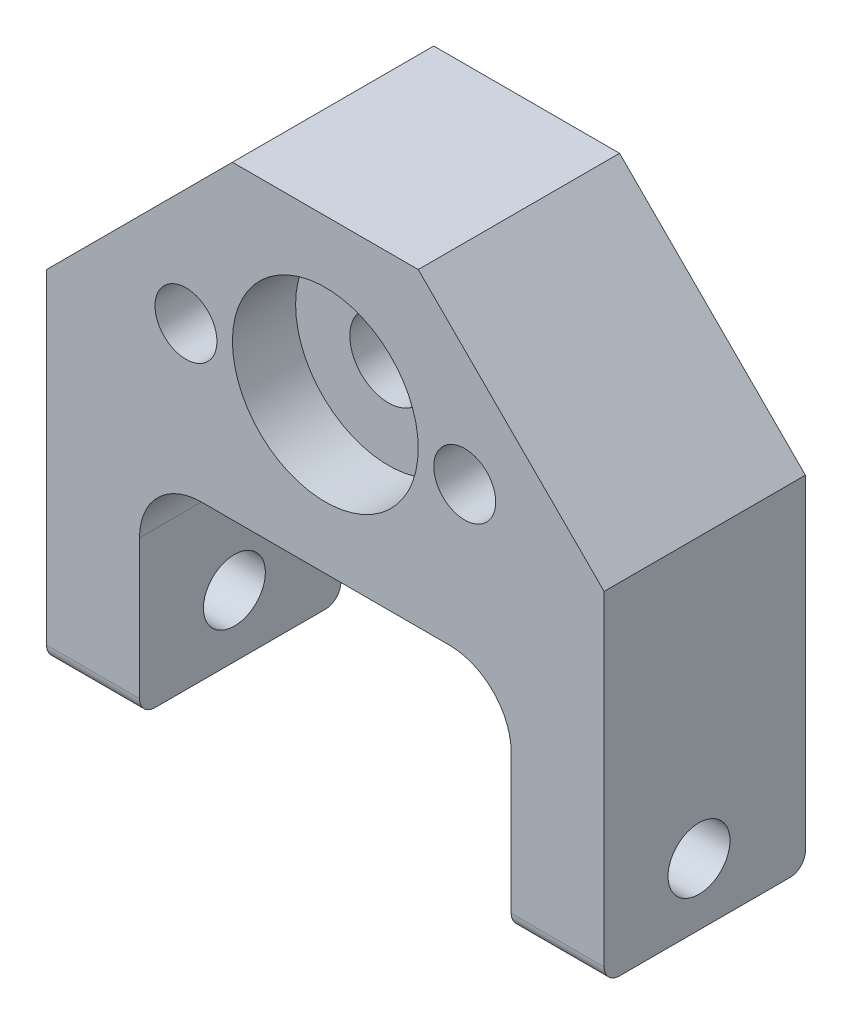
SolidWorks part; units mm, degrees
material "6063-O"
ref_plane "Front" through (0, 0, 0) normal (0, 0, 1) x (1, 0, 0)
ref_plane "Top" through (0, 0, 0) normal (0, 1, 0) x (1, 0, 0)
ref_plane "Right" through (0, 0, 0) normal (1, 0, 0) x (0, 0, -1)
sketch "Sketch1" plane through (0, 0, 0) normal (0, 0, 1) x (1, 0, 0)
  line L1 (28.575, -15.875) -> (-28.575, -15.875)
  line L2 (28.575, -15.875) -> (28.575, 15.875)
  line L3 (28.575, 15.875) -> (-28.575, 15.875)
  line L4 (-28.575, -15.875) -> (-28.575, 15.875)
  line L5 (28.575, -15.875) -> (-28.575, 15.875) construction
  line L6 (28.575, 15.875) -> (-28.575, -15.875) construction
  point P0 (0, 0)
  dimension "D1" = 31.75
  dimension "D2" = 57.15
extrude "Boss-Extrude1" add sketch "Sketch1" along normal blind 20.6375
sketch "Sketch2" plane through (0, 0, 0) normal (0, 0, -1) x (-1, 0, 0)
  circle A0 centre (0, 0) radius 11.1125
  dimension "D1" = 22.225
extrude "Cut-Extrude1" cut sketch "Sketch2" against normal blind 6.985
sketch "Sketch3" plane through (0, 0, 6.985) normal (0, 0, -1) x (-1, 0, 0)
  circle A0 centre (0, 0) radius 8.255
  dimension "D1" = 16.51
extrude "Cut-Extrude2" cut sketch "Sketch3" against normal blind 2.413
sketch "Sketch4" plane through (0, 0, 9.398) normal (0, 0, -1) x (-1, 0, 0)
  circle A0 centre (0, 0) radius 3.9688
  dimension "D1" = 7.9375
extrude "Cut-Extrude3" cut sketch "Sketch4" against normal through all
sketch "Sketch6" plane through (0, 0, 9.398) normal (0, 0, -1) x (-1, 0, 0)
  circle A0 centre (0, 0) radius 9.525
  dimension "D1" = 19.05
extrude "Cut-Extrude4" cut sketch "Sketch6" against normal through all from offset 4.7625 offset against normal yes
sketch "Sketch7" plane through (0, -15.875, 0) normal (0, -1, 0) x (1, 0, 0)
  line L0 (-28.575, 0) -> (28.575, 0) construction
  line L1 (-28.575, 20.6375) -> (-19.05, 20.6375)
  line L2 (-28.575, 20.6375) -> (-28.575, 0)
  line L3 (-28.575, 0) -> (-19.05, 0)
  line L4 (-19.05, 20.6375) -> (-19.05, 0)
  line L6 (28.575, 20.6375) -> (19.05, 20.6375)
  line L7 (28.575, 20.6375) -> (28.575, 0)
  line L8 (28.575, 0) -> (19.05, 0)
  line L9 (19.05, 20.6375) -> (19.05, 0)
  dimension "D1" = 9.525
extrude "Boss-Extrude2" add sketch "Sketch7" along normal blind 22.225
sketch "Sketch9" plane through (28.575, 0, 0) normal (1, 0, 0) x (0, 0, -1)
  line L0 (0, -38.1) -> (-20.6375, -38.1) construction
  circle A0 centre (-10.9095, -31.75) radius 3.175
  dimension "D2" = 6.35
  dimension "D1" = 6.35
extrude "Cut-Extrude5" cut sketch "Sketch9" against normal through all
fillet "Fillet1" radius 6.35 2 edges at (19.05, -15.875, 10.3187) (-19.05, -15.875, 10.3187)
hole_wizard "1/4 (0.2500) Dowel Hole1" positions "Sketch10" profile "Sketch11" hole size "1/4" standard "ANSI Inch"
sketch "Sketch10" plane through (0, 0, 20.6375) normal (0, 0, 1) x (1, 0, 0)
  line L0 (-28.575, 15.875) -> (-28.575, -38.1) construction
  line L1 (28.575, -38.1) -> (28.575, 15.875) construction
  line L2 (28.575, 15.875) -> (-28.575, 15.875) construction
  point P0 (-14.2875, -0.8255)
  point P2 (14.2875, -0.8052)
  dimension "D1" = 14.2875
  dimension "D2" = 14.2875
  dimension "D3" = 16.7005
  dimension "D4" = 16.6802
sketch "Sketch11" plane through (-14.2875, -0.8255, 20.6375) normal (1, 0, 0) x (0, -1, 0)
  line L0 (0, 0) -> (0, 11.5597)
  line L1 (0, 11.5597) -> (3.175, 9.652)
  line L2 (3.175, 9.652) -> (3.175, 0)
  line L5 (3.175, 0) -> (0, 0)
  line L10 (0, 11.5597) -> (-3.175, 9.652) construction
  line L11 (0, -6.35) -> (0, 107.95) construction
  dimension "Hole Dia." = 6.35
  dimension "Hole Depth" = 9.652
  dimension "Drill Angle" = 118
fillet "Fillet3" radius 1.5875 4 edges at (23.8125, -38.1, 0) (23.8125, -38.1, 20.6375) (-23.8125, -38.1, 20.6375) (-23.8125, -38.1, 0)
chamfer "Chamfer1" distance 19.05 angle 45 2 edges at (28.575, 15.875, 10.3187) (-28.575, 15.875, 10.3187)
